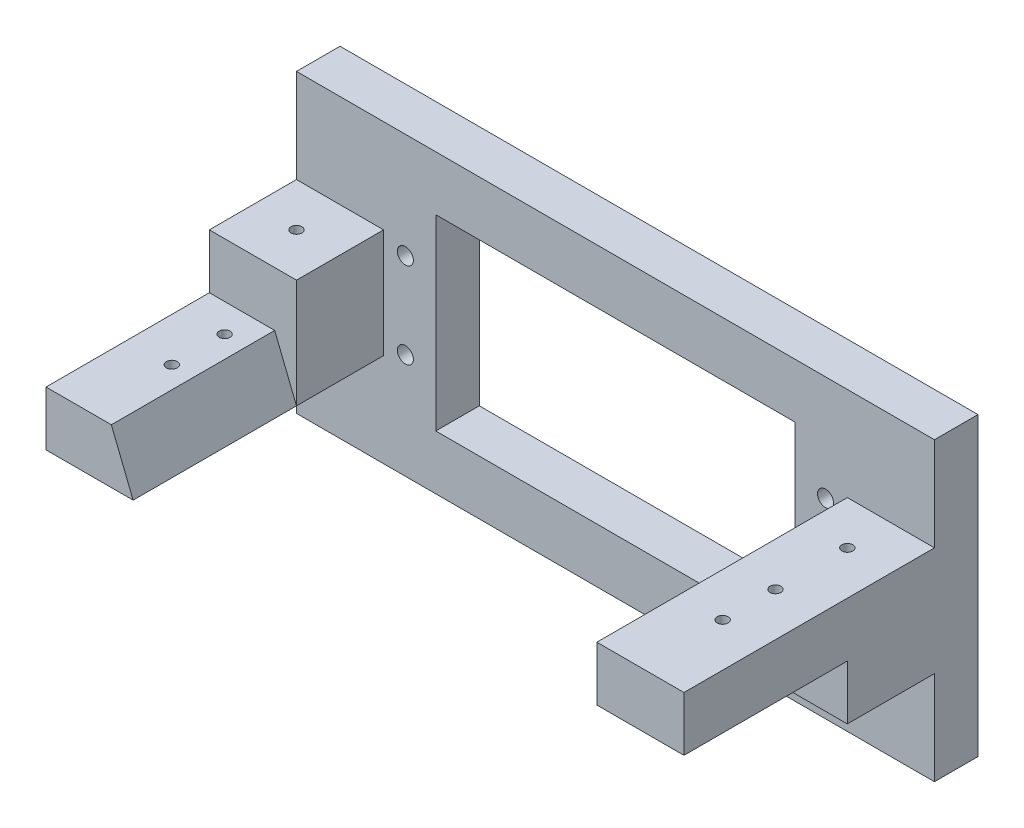
SolidWorks part; units mm, degrees
ref_plane "Front Plane" through (0, 0, 0) normal (0, 0, 1) x (1, 0, 0)
ref_plane "Top Plane" through (0, 0, 0) normal (0, 1, 0) x (1, 0, 0)
ref_plane "Right Plane" through (0, 0, 0) normal (1, 0, 0) x (0, 0, -1)
sketch "Sketch1" plane through (0, 0, 0) normal (0, 0, 1) x (1, 0, 0)
  line L1 (0, 0) -> (54.61, 0)
  line L2 (0, 0) -> (0, 47.244)
  line L3 (0, 47.244) -> (54.61, 47.244)
  line L4 (54.61, 0) -> (54.61, 47.244)
  line L5 (6.35, 12.7) -> (48.26, 12.7)
  line L6 (6.35, 12.7) -> (6.35, 34.544)
  line L7 (6.35, 34.544) -> (48.26, 34.544)
  line L8 (48.26, 12.7) -> (48.26, 34.544)
  dimension "D1" = 41.91
  dimension "D2" = 21.844
  dimension "D3" = 6.35
  dimension "D4" = 6.35
  dimension "D5" = 12.7
  dimension "D6" = 12.7
extrude "Boss-Extrude1" add sketch "Sketch1" along normal blind 5.08
sketch "Sketch2" plane through (0, 0, 5.08) normal (0, 0, 1) x (1, 0, 0)
  line L0 (0, 23.622) -> (54.61, 23.622) construction
  line L1 (2.8054, 28.622) -> (51.8046, 28.622) construction
  line L2 (2.8054, 28.622) -> (2.8054, 18.622) construction
  line L3 (2.8054, 18.622) -> (51.8046, 18.622) construction
  line L4 (51.8046, 28.622) -> (51.8046, 18.622) construction
  line L5 (0, 47.244) -> (0, 0) construction
  line L6 (54.61, 0) -> (54.61, 47.244) construction
  line L7 (2.8054, 23.622) -> (51.8046, 23.622) construction
  line L8 (27.305, 28.622) -> (27.305, 18.622) construction
  line L9 (27.305, 47.244) -> (27.305, 0) construction
  line L10 (54.61, 47.244) -> (0, 47.244) construction
  line L11 (0, 0) -> (54.61, 0) construction
  line L12 (25.1752, 42.164) -> (29.4348, 42.164) construction
  line L13 (29.4348, 42.164) -> (29.4348, 5.08) construction
  line L14 (29.4348, 5.08) -> (25.1752, 5.08) construction
  line L15 (25.1752, 5.08) -> (25.1752, 42.164) construction
  line L16 (48.26, 34.544) -> (6.35, 34.544) construction
  line L17 (6.35, 12.7) -> (48.26, 12.7) construction
  circle A0 centre (2.8054, 28.622) radius 0.936
  circle A1 centre (2.8054, 18.622) radius 0.936
  circle A2 centre (51.8046, 28.622) radius 0.936
  circle A3 centre (51.8046, 18.622) radius 0.936
  circle A4 centre (25.1752, 5.08) radius 0.635 construction
  circle A5 centre (29.4348, 5.08) radius 0.635 construction
  circle A6 centre (29.4348, 42.164) radius 0.635 construction
  circle A7 centre (25.1752, 42.164) radius 0.635 construction
  point P16 (2.8054, 27.686)
  point P17 (2.8054, 19.558)
  dimension "D2" = 8.128
  dimension "D4" = 1.872
  dimension "D5" = 1.27
  dimension "D1" = 10
  dimension "D3" = 48.9991
  dimension "D6" = 4.2596
  dimension "D7" = 2.1298
  dimension "D8" = 7.62
  dimension "D9" = 7.62
  dimension "D10" = 37.084
extrude "Cut-Extrude1" cut sketch "Sketch2" against normal through all
sketch "Sketch10" plane through (0, 0, 5.08) normal (0, 0, 1) x (1, 0, 0)
  line L0 (0, 47.244) -> (0, 80.7756)
  line L1 (0, 80.7756) -> (-31.1018, 80.7756)
  line L2 (0, 47.244) -> (0, 0)
  line L3 (-31.1018, 80.7756) -> (-31.1018, -10.4159)
  line L4 (-31.1018, -10.4159) -> (0, -10.4159)
  line L5 (0, 23.622) -> (54.61, 23.622) construction
  line L6 (54.61, 0) -> (54.61, 47.244) construction
  line L7 (54.61, 23.622) -> (62.23, 23.622) construction
  line L8 (62.23, 23.622) -> (66.4896, 23.622)
  line L9 (-13.8825, 79.8399) -> (-11.43, 79.8399)
  line L10 (-13.8825, 79.8399) -> (-13.8825, 3.6399)
  line L11 (-13.8825, 3.6399) -> (-11.43, 3.6399)
  line L12 (-11.43, 79.8399) -> (-11.43, 3.6399)
  line L13 (0, -10.4159) -> (0, 47.244)
  line L14 (69.0296, 23.622) -> (66.4896, 23.622) construction
  line L15 (0, 47.244) -> (0, 0) construction
  line L16 (64.3598, 25.7518) -> (64.3598, 21.4922) construction
  line L17 (54.61, 33.3718) -> (69.0296, 33.3718)
  line L18 (54.61, 33.3718) -> (54.61, 13.8722)
  line L19 (54.61, 13.8722) -> (69.0296, 13.8722)
  line L20 (69.0296, 33.3718) -> (69.0296, 13.8722)
  line L21 (0, 0) -> (54.61, 0) construction
  line L23 (54.61, 13.1354) -> (54.5843, 13.1354)
  circle A0 centre (-6.7996, 44.704) radius 0.635
  circle A1 centre (-2.54, 44.704) radius 0.635
  circle A2 centre (62.23, 23.622) radius 0.635 construction
  circle A3 centre (66.4896, 23.622) radius 0.635 construction
  circle A4 centre (64.3598, 25.7518) radius 0.635
  circle A5 centre (64.3598, 21.4922) radius 0.635
  point P27 (64.3598, 23.622)
  line M9 (54.61, 0) -> (54.61, 47.244)
  dimension "D1" = 1.27
  dimension "D10" = 13.8825
  dimension "D11" = 31.1018
  dimension "D2" = 4.2596
  dimension "D3" = 7.62
  dimension "D4" = 2.54
  dimension "D5" = 7.62
  dimension "D6" = 76.2
  dimension "D7" = 2.54
  dimension "D8" = 11.43
  dimension "D9" = 54.5843
  dimension "D12" = 3.6399
  dimension "D13" = 13.1354
  dimension "D14" = 44.704
  dimension "D15" = 80.7756
  dimension "D16" = 10.4159
  dimension "D17" = 4.2596
extrude "Boss-Extrude4" add sketch "Sketch10" against normal up to surface (5.08 mm away) contours A2 A3 M9 region at (61.7967, 23.622, 5.08) up to face at (52.7406, 18.622, 0)
sketch "Sketch11" plane through (0, 0, 5.08) normal (0, 0, 1) x (1, 0, 0)
  line L0 (0, 47.244) -> (-5.842, 47.244)
  line L1 (-5.842, 47.244) -> (-5.842, 64.262)
  line L2 (-5.842, 64.262) -> (-15.748, 64.262)
  line L3 (-15.748, 64.262) -> (-15.748, -17.018)
  line L4 (-15.748, -17.018) -> (-4.572, -17.018)
  line L5 (-4.572, -17.018) -> (-4.572, 0)
  line L6 (-4.572, 0) -> (0, 0)
  line L7 (0, 0) -> (0, 47.244)
  line L11 (-9.144, 61.722) -> (-5.842, 61.722) construction
  line L12 (-12.446, 61.722) -> (-9.144, 61.722)
  line L13 (-12.446, 61.722) -> (-12.446, -14.478)
  line L14 (-12.446, -14.478) -> (-9.144, -14.478)
  line L15 (-9.144, 61.722) -> (-9.144, -14.478)
  line L16 (-12.446, 61.722) -> (-15.748, 61.722) construction
  line L17 (-12.446, 61.722) -> (-12.446, 64.262) construction
  line L18 (-12.446, -14.478) -> (-12.446, -17.018) construction
  line L19 (0, 47.244) -> (0, 0) construction
  line L20 (0, 0) -> (54.61, 0) construction
  circle A0 centre (64.3598, 25.7518) radius 0.635 construction
  circle A1 centre (64.3598, 21.4922) radius 0.635 construction
  circle A2 centre (64.3598, 25.7518) radius 0.635 construction
  circle A3 centre (64.3598, 21.4922) radius 0.635 construction
  circle A4 centre (-4.572, 21.4922) radius 0.635
  circle A5 centre (-4.572, 25.7518) radius 0.635
  dimension "D10" = 1.27
  dimension "D1" = 76.2
  dimension "D2" = 4.572
  dimension "D3" = 4.572
  dimension "D4" = 3.302
  dimension "D5" = 3.302
  dimension "D6" = 81.28
  dimension "D7" = 15.748
  dimension "D8" = 4.572
  dimension "D9" = 0
  dimension "D11" = 4.2596
  dimension "D12" = 4.572
  dimension "D13" = 21.4922
extrude "Boss-Extrude5" add sketch "Sketch11" against normal up to surface (5.08 mm away) up to face at (52.7406, 18.622, 0)
sketch "Sketch12" plane through (0, 0, 5.08) normal (0, 0, 1) x (1, 0, 0)
  line L0 (54.61, 33.3718) -> (54.61, 47.244) construction
  line L1 (-5.842, 47.244) -> (54.61, 47.244)
  line L2 (-5.842, 47.244) -> (-5.842, 40.894)
  line L3 (-5.842, 40.894) -> (54.61, 40.894)
  line L4 (54.61, 47.244) -> (54.61, 40.894)
  line L5 (54.61, 0) -> (54.61, 13.8722) construction
  line L6 (-4.572, 0) -> (54.61, 0)
  line L7 (-4.572, 0) -> (-4.572, 6.35)
  line L8 (-4.572, 6.35) -> (54.61, 6.35)
  line L9 (54.61, 0) -> (54.61, 6.35)
  line L10 (6.35, 12.7) -> (48.26, 12.7) construction
  line L11 (48.26, 34.544) -> (6.35, 34.544) construction
  line L12 (48.26, 12.7) -> (48.26, 34.544) construction
  line L13 (48.26, 12.7) -> (48.26, 34.544) construction
  dimension "D1" = 6.35
  dimension "D2" = 6.35
  dimension "D3" = 6.35
extrude "Cut-Extrude2" cut sketch "Sketch12" against normal through all
sketch "Sketch13" plane through (0, 0, 0) normal (0, 0, -1) x (-1, 0, 0)
  line L0 (15.748, 64.262) -> (15.748, -17.018) construction
  line L1 (7.1554, 62.8847) -> (14.175, 62.8847)
  line L2 (7.1554, 62.8847) -> (7.1554, -16.1087)
  line L3 (7.1554, -16.1087) -> (14.175, -16.1087)
  line L4 (14.175, 62.8847) -> (14.175, -16.1087)
  line L5 (9.144, 61.722) -> (12.446, 61.722) construction
  line L6 (12.446, -14.478) -> (9.144, -14.478) construction
  dimension "D1" = 7.0196
  dimension "D2" = 1.573
  dimension "D3" = 1.1627
  dimension "D4" = 1.6307
extrude "Boss-Extrude6" add sketch "Sketch13" against normal offset from surface (4.826 mm away) 0.254 up to face at (52.7406, 18.622, 5.08)
fillet "Fillet1" radius 2.54 12 edges at (69.0296, 13.8722, 2.54) (54.61, 6.35, 2.54) (-4.572, 6.35, 2.54) (-4.572, -17.018, 2.54) (-15.748, -17.018, 2.54) (-15.748, 64.262, 2.54) (-5.842, 64.262, 2.54) (-5.842, 40.894, 2.54) (54.61, 40.894, 2.54) (69.0296, 33.3718, 2.54)
sketch "Sketch14" plane through (0, 0, 5.08) normal (0, 0, 1) x (1, 0, 0)
  line L0 (2.8054, 28.622) -> (2.8054, 40.894) construction
  line L1 (-3.302, 40.894) -> (52.07, 40.894) construction
  line L2 (2.8054, 40.894) -> (-0.8159, 40.894)
  line L3 (-0.8159, 40.894) -> (-0.8159, 6.35)
  line L5 (52.07, 6.35) -> (-2.032, 6.35) construction
  line L6 (-0.8159, 6.35) -> (2.8054, 6.35)
  line L7 (2.8054, 6.35) -> (2.8054, -19.9418)
  line L8 (2.8054, -19.9418) -> (-23.5153, -19.9418)
  line L9 (-23.5153, -19.9418) -> (-23.5153, 65.8265)
  line L10 (-23.5153, 65.8265) -> (2.8054, 65.8265)
  line L11 (2.8054, 65.8265) -> (2.8054, 40.894)
  line L12 (51.8046, 28.622) -> (51.8046, 40.8969) construction
  line L13 (51.8046, 40.8969) -> (51.8046, 65.8265)
  line L14 (51.8046, 65.8265) -> (74.4862, 65.8265)
  line L15 (74.4862, 65.8265) -> (74.4862, -19.9418)
  line L16 (74.4862, -19.9418) -> (51.8046, -19.9418)
  line L17 (51.8046, -19.9418) -> (52.07, 6.35)
  line L18 (52.07, 6.35) -> (54.61, 8.89)
  line L19 (54.61, 8.89) -> (54.61, 38.354)
  line L20 (54.61, 38.354) -> (51.8046, 40.8969)
  line L21 (-15.748, 61.722) -> (-15.748, -14.478) construction
  line L22 (-8.382, 64.262) -> (-13.208, 64.262) construction
  dimension "D1" = 14.9321
  dimension "D2" = 90.2342
  dimension "D3" = 7.7673
  dimension "D4" = 1.5645
  dimension "D5" = 23.3651
  dimension "D6" = 84.2038
extrude "Cut-Extrude3" cut sketch "Sketch14" against normal through all
sketch "Sketch15" plane through (0, 0, 5.08) normal (0, 0, 1) x (1, 0, 0)
  line L0 (-0.8159, 40.894) -> (-9.8946, 40.894)
  line L1 (-9.8946, 40.894) -> (-9.8946, 6.35)
  line L2 (-9.8946, 6.35) -> (-0.8159, 6.35)
  line L3 (-0.8159, 6.35) -> (-0.8159, 40.894) construction
  line L4 (-0.8159, 6.35) -> (-0.8159, 40.894)
  line L5 (51.8077, 40.894) -> (54.61, 38.354)
  line L6 (54.61, 38.354) -> (54.61, 8.89)
  line L7 (54.61, 8.89) -> (54.61, 38.354) construction
  line L8 (54.61, 8.89) -> (52.07, 6.35)
  line L9 (52.07, 6.35) -> (64.5046, 6.35)
  line L10 (64.5046, 6.35) -> (64.5046, 40.894)
  line L11 (64.5046, 40.894) -> (51.8077, 40.894)
  circle A0 centre (2.8054, 28.622) radius 0.936 construction
  circle A1 centre (2.8054, 28.622) radius 0.936 construction
  circle A2 centre (51.8046, 28.622) radius 0.936 construction
  circle A3 centre (51.8046, 28.622) radius 0.936 construction
  dimension "D1" = 12.7
  dimension "D2" = 3.6214
  dimension "D3" = 12.7
extrude "Boss-Extrude7" add sketch "Sketch15" against normal up to surface (5.08 mm away) up to face at (35.2443, 21.1667, 0)
sketch "Sketch16" plane through (0, 0, 5.08) normal (0, 0, 1) x (1, 0, 0)
  line L0 (-9.8946, 40.894) -> (-9.8946, 6.35) construction
  line L1 (-9.8946, 17.272) -> (0.2654, 17.272)
  line L2 (-9.8946, 17.272) -> (-9.8946, 29.972)
  line L3 (-9.8946, 29.972) -> (0.2654, 29.972)
  line L4 (0.2654, 17.272) -> (0.2654, 29.972)
  line L5 (0.2654, 17.272) -> (54.3446, 17.272) construction
  line L6 (64.5046, 6.35) -> (64.5046, 40.894) construction
  line L7 (54.3446, 17.272) -> (64.5046, 17.272)
  line L8 (54.3446, 17.272) -> (54.3446, 29.972)
  line L9 (54.3446, 29.972) -> (64.5046, 29.972)
  line L10 (64.5046, 17.272) -> (64.5046, 29.972)
  line L11 (54.3446, 29.972) -> (0.2654, 29.972) construction
  line L12 (6.35, 23.622) -> (48.26, 23.622) construction
  line L13 (6.35, 34.544) -> (6.35, 12.7) construction
  line L14 (48.26, 12.7) -> (48.26, 34.544) construction
  line L15 (6.35, 23.622) -> (0.2654, 23.622) construction
  dimension "D1" = 10.16
  dimension "D2" = 12.7
extrude "Boss-Extrude8" add sketch "Sketch16" along normal blind 10.16
sketch "Sketch17" plane through (0, 29.972, 0) normal (0, 1, 0) x (1, 0, 0)
  line L0 (-4.8146, -10.16) -> (-4.8146, -5.08) construction
  line L4 (0.2654, -5.08) -> (-9.8946, -5.08) construction
  line L5 (59.4246, -5.08) -> (59.4246, -10.16) construction
  line L6 (64.5046, -5.08) -> (54.3446, -5.08) construction
  circle A0 centre (-4.8146, -10.16) radius 1.5875 construction
  circle A1 centre (-4.8146, -10.16) radius 0.635
  circle A2 centre (59.4246, -10.16) radius 0.635
  dimension "D1" = 3.175
  dimension "D2" = 1.27
  dimension "D5" = 1.27
  dimension "D3" = 5.08
  dimension "D4" = 5.08
extrude "Cut-Extrude4" cut sketch "Sketch17" against normal through all
ref_plane "Plane1" through (0, 0, 28.001) normal (0, 0, 1) x (1, 0, 0)
sketch "Sketch18" plane through (0, 0, 15.24) normal (0, 0, 1) x (1, 0, 0)
  line L0 (-9.8946, 23.622) -> (0.2654, 23.622) construction
  line L1 (-9.8946, 29.972) -> (-9.8946, 17.272) construction
  line L2 (0.2654, 17.272) -> (0.2654, 29.972) construction
  line L3 (0.2654, 23.622) -> (54.3446, 23.622) construction
  line L4 (54.3446, 29.972) -> (54.3446, 17.272) construction
  line L5 (54.3446, 23.622) -> (64.5046, 23.622) construction
  line L6 (64.5046, 17.272) -> (64.5046, 29.972) construction
  line L8 (-9.8946, 23.622) -> (0.2654, 23.622)
  line L9 (-9.8946, 23.622) -> (-9.8946, 17.272)
  line L10 (-9.8946, 17.272) -> (0.2654, 17.272)
  line L11 (0.2654, 23.622) -> (0.2654, 17.272)
  line L12 (54.3446, 23.622) -> (64.5046, 23.622)
  line L13 (54.3446, 23.622) -> (54.3446, 29.972)
  line L14 (54.3446, 29.972) -> (64.5046, 29.972)
  line L15 (64.5046, 23.622) -> (64.5046, 29.972)
extrude "Boss-Extrude9" add sketch "Sketch18" along normal up to surface (12.761 mm away) up to plane "Plane1"
sketch "Sketch19" plane through (0, 23.622, 0) normal (0, 1, 0) x (1, 0, 0)
  line L0 (-4.8146, -15.24) -> (-4.8146, -18.542) construction
  line L1 (-18.9992, -28.001) -> (18.9992, -28.001) construction
  line L2 (59.4246, -10.795) -> (59.4246, -28.001) construction
  line L3 (0.2654, -15.24) -> (-9.8946, -15.24) construction
  line L4 (-4.8146, -18.542) -> (-4.8146, -24.699) construction
  line L6 (-4.8146, -24.699) -> (-4.8146, -28.001) construction
  circle A0 centre (-4.8146, -10.16) radius 0.635 construction
  circle A1 centre (59.4246, -10.16) radius 0.635 construction
  circle A2 centre (-4.8146, -18.542) radius 0.635
  circle A3 centre (-4.8146, -24.699) radius 0.635
  circle A4 centre (59.4246, -18.542) radius 0.635
  circle A5 centre (59.4246, -24.699) radius 0.635
  circle A6 centre (-4.8146, -10.16) radius 0.635 construction
  dimension "D1" = 1.27
  dimension "D2" = 3.302
  dimension "D3" = 3.302
  dimension "D4" = 6.157
  dimension "D5" = 3.302
  dimension "D6" = 6.157
extrude "Cut-Extrude5" cut sketch "Sketch19" against normal through all and the other way through all
sketch "Sketch20" plane through (0, 0, 28.001) normal (0, 0, 1) x (1, 0, 0)
  line L0 (0.2654, 23.622) -> (-9.8946, 23.622) construction
  line L1 (0.2654, 17.272) -> (0.2654, 23.622) construction
  line L2 (-9.8946, 17.272) -> (0.2654, 17.272) construction
  line L3 (-9.8946, 23.622) -> (-9.8946, 17.272) construction
  line L4 (54.3446, 29.972) -> (54.3446, 23.622) construction
  line L5 (64.5046, 29.972) -> (54.3446, 29.972) construction
  line L6 (64.5046, 23.622) -> (64.5046, 29.972) construction
  line L7 (54.3446, 23.622) -> (64.5046, 23.622) construction
  line L8 (0.2654, 23.622) -> (-9.8946, 23.622)
  line L9 (0.2654, 17.272) -> (0.2654, 23.622)
  line L10 (-9.8946, 17.272) -> (0.2654, 17.272)
  line L11 (-9.8946, 23.622) -> (-9.8946, 17.272)
  line L12 (54.3446, 29.972) -> (54.3446, 23.622)
  line L13 (64.5046, 29.972) -> (54.3446, 29.972)
  line L14 (64.5046, 23.622) -> (64.5046, 29.972)
  line L15 (54.3446, 23.622) -> (64.5046, 23.622)
extrude "Boss-Extrude10" add sketch "Sketch20" along normal blind 6.289
sketch "Sketch22" plane through (0, 0, 34.29) normal (0, 0, 1) x (1, 0, 0)
  line L0 (0.2654, 17.272) -> (-2.2746, 23.622)
  line L1 (0.2654, 23.622) -> (-9.8946, 23.622) construction
  line L2 (-2.2746, 23.622) -> (0.2654, 23.622)
  line L3 (0.2654, 17.272) -> (0.2654, 29.972) construction
  line L4 (0.2654, 23.622) -> (0.2654, 17.272)
  dimension "D1" = 2.54
extrude "Cut-Extrude7" cut sketch "Sketch22" against normal up to surface (19.05 mm away) up to face at (-3.5446, 26.797, 15.24)
equation "\"D7@Sketch2\"=\"D6@Sketch2\"/2"
equation "\"D8@Sketch11\" = \"D2@Sketch11\""
equation "\"D1@Sketch12\"=\"D3@Sketch12\""
equation "\"D2@Sketch12\"= \"D1@Sketch12\""
equation "\"D3@Sketch11\"= \"D2@Sketch11\""
equation "\"D5@Sketch17\"=\"D2@Sketch17\""
equation "\"D5@Sketch19\"=\"D3@Sketch19\""
equation "\"D6@Sketch19\"=\"D4@Sketch19\""
